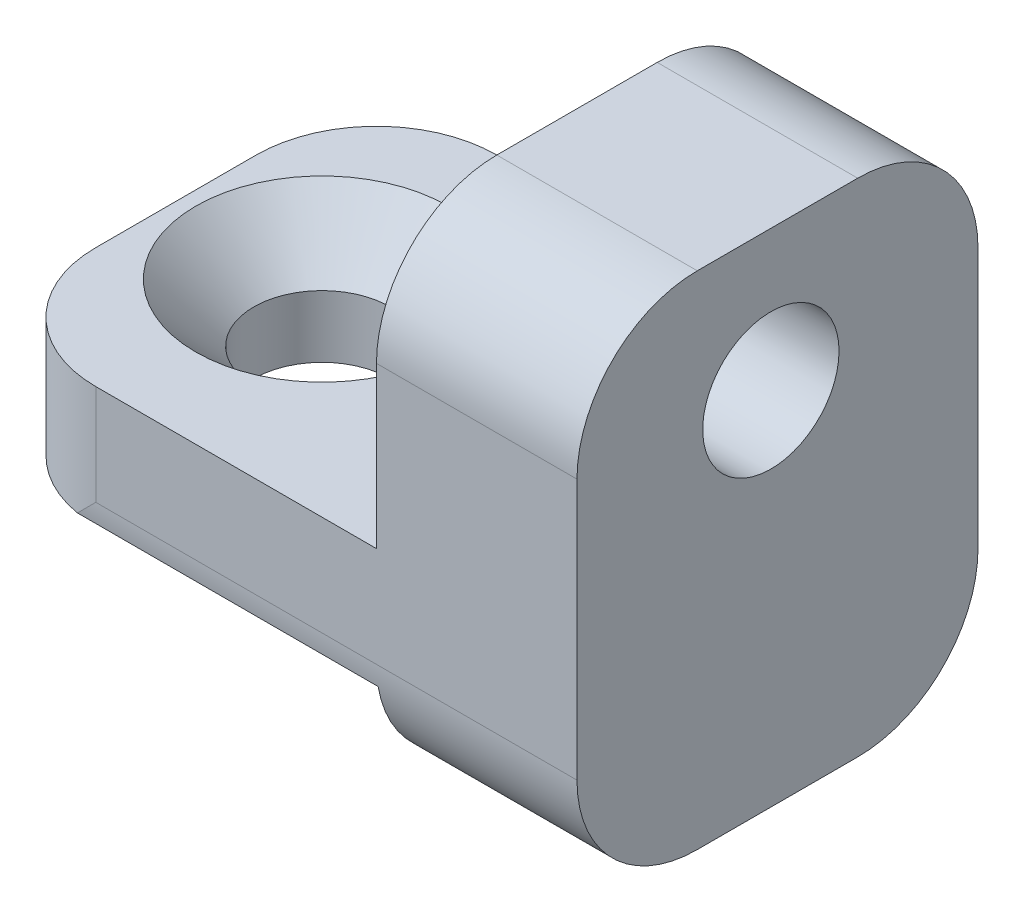
SolidWorks part; units mm, degrees
ref_plane "Plan de face" through (0, 0, 0) normal (0, 0, 1) x (1, 0, 0)
ref_plane "Plan de dessus" through (0, 0, 0) normal (0, 1, 0) x (1, 0, 0)
ref_plane "Plan de droite" through (0, 0, 0) normal (1, 0, 0) x (0, 0, -1)
sketch "Esquisse1" plane through (0, 0, 0) normal (0, 0, 1) x (1, 0, 0)
  line L1 (0, 0) -> (15, 0) construction
  line L2 (0, 0) -> (0, 10) construction
  line L3 (0, 10) -> (15, 10) construction
  line L4 (15, 0) -> (15, 10) construction
  line L5 (15, 0) -> (15, 10)
  line L6 (15, 10) -> (10, 10)
  line L7 (10, 10) -> (10, 3)
  line L8 (10, 3) -> (0, 3)
  line L9 (0, 3) -> (0, 0)
  line L10 (0, 0) -> (10, 0)
  line L11 (10, 0) -> (10, -2.5)
  line L12 (10, -2.5) -> (15, -2.5)
  line L13 (15, -2.5) -> (15, 0)
  dimension "D1" = 15
  dimension "D2" = 10
  dimension "D3" = 5
  dimension "D4" = 3
  dimension "D5" = 2.5
  dimension "D6" = 5
extrude "Boss.-Extru.1" add sketch "Esquisse1" along normal blind 10
sketch "Esquisse2" plane through (15, 0, 0) normal (1, 0, 0) x (0, 0, -1)
  line L0 (-10, 10) -> (0, 10) construction
  circle A0 centre (-5.1651, 6.5) radius 1.5
  dimension "D2" = 3
  dimension "D1" = 3.5
extrude "Enlèv. mat.-Extru.1" cut sketch "Esquisse2" against normal up to surface (5 mm away) up to face at (10, 6.5, 5)
sketch "Esquisse3" plane through (0, 3, 0) normal (0, 1, 0) x (1, 0, 0)
  line L0 (0, -10) -> (0, 0) construction
  circle A0 centre (3.5, -4.8584) radius 1.5
  dimension "D2" = 3
  dimension "D1" = 3.5
extrude "Enlèv. mat.-Extru.2" cut sketch "Esquisse3" against normal up to surface (3 mm away) up to face at (5, 0, 5)
hole_wizard "Dégagement M31" positions "Esquisse4" profile "Esquisse5" hole size "M3" standard "ISO"
sketch "Esquisse4" plane through (15, 0, 0) normal (1, 0, 0) x (0, 0, -1)
  point P0 (-5.1651, 6.5)
sketch "Esquisse5" plane through (15, 6.5, 5.1651) normal (0, 1, 0) x (0, 0, -1)
  line L0 (0, 0) -> (0, 6.0215)
  line L1 (0, 6.0215) -> (1.7, 5)
  line L2 (1.7, 5) -> (1.7, 0)
  line L5 (1.7, 0) -> (0, 0)
  line L10 (0, 6.0215) -> (-1.7, 5) construction
  line L11 (0, -6.35) -> (0, 107.95) construction
  dimension "Diamètre du perçage" = 3.4
  dimension "Profondeur du perçage" = 5
  dimension "Angle de pointe" = 118
hole_wizard "Fraisage pour vis à tête fraisée M31" positions "Esquisse6" profile "Esquisse7" countersink size "M3" standard "ISO"
sketch "Esquisse6" plane through (0, 3, 0) normal (0, 1, 0) x (1, 0, 0)
  point P0 (3.5, -4.8584)
sketch "Esquisse7" plane through (3.5, 3, 4.8584) normal (1, 0, 0) x (0, 0, 1)
  line L0 (0, 0) -> (0, 4.0215)
  line L1 (0, 4.0215) -> (1.7, 3)
  line L2 (1.7, 3) -> (1.7, 1.45)
  line L3 (1.7, 1.45) -> (3.15, 0)
  line L5 (3.15, 0) -> (0, 0)
  line L6 (-1.7, 1.45) -> (-3.15, 0) construction
  line L10 (0, 4.0215) -> (-1.7, 3) construction
  line L11 (0, -6.35) -> (0, 107.95) construction
  dimension "Diamètre du perçage" = 3.4
  dimension "Profondeur du perçage" = 3
  dimension "Diamètre du fraisage entrant" = 6.3
  dimension "Angle du fraisage entrant" = 90
  dimension "Angle de pointe" = 118
fillet "Congé1" radius 3 6 edges at (0, 1.5, 10) (0, 1.5, 0) (12.5, 10, 0) (12.5, 10, 10) (12.5, -2.5, 0) (12.5, -2.5, 10)
